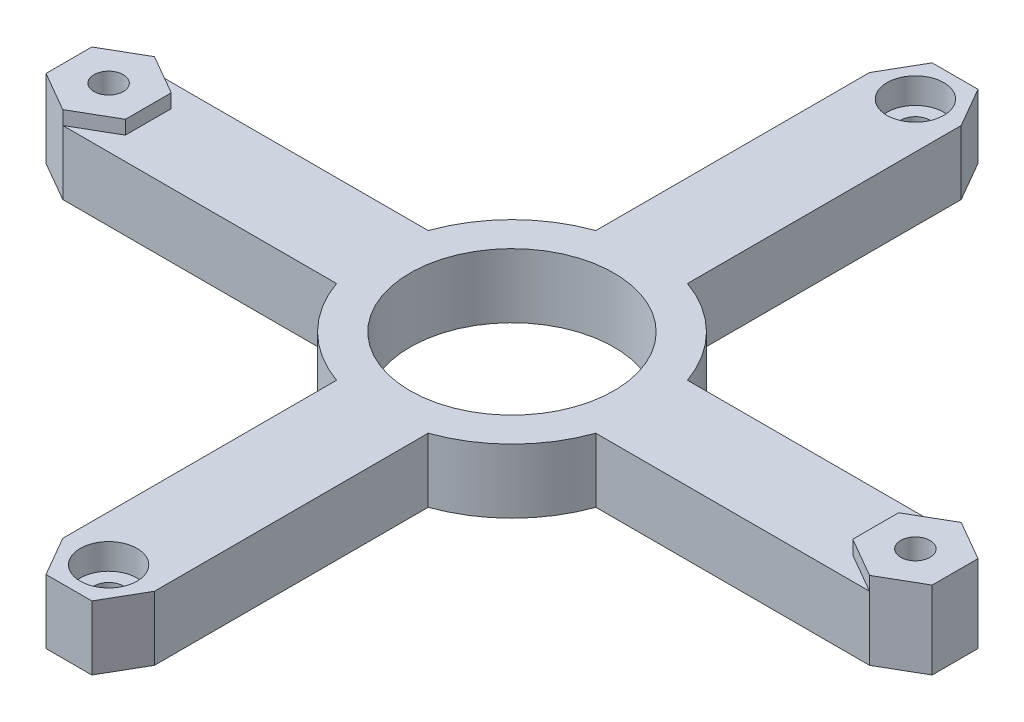
SolidWorks part; units mm, degrees
ref_plane "Front Plane" through (0, 0, 0) normal (0, 0, 1) x (1, 0, 0)
ref_plane "Top Plane" through (0, 0, 0) normal (0, 1, 0) x (1, 0, 0)
ref_plane "Right Plane" through (0, 0, 0) normal (1, 0, 0) x (0, 0, -1)
sketch "Sketch1" plane through (0, 0, 0) normal (0, 1, 0) x (1, 0, 0)
  line L0 (0, 0) -> (0, 2984.5753) construction
  line L1 (0, 0) -> (2984.5753, 0) construction
  line L7 (44, 5) -> (48.3301, 2.5)
  line L8 (48.3301, 2.5) -> (48.3301, -2.5)
  line L13 (48.3301, -2.5) -> (44, -5)
  line L14 (5, -44) -> (2.5, -48.3301)
  line L15 (14.1421, 5) -> (44, 5)
  line L16 (2.5, -48.3301) -> (-2.5, -48.3301)
  line L17 (-2.5, -48.3301) -> (-5, -44)
  line L18 (14.1421, -5) -> (44, -5)
  line L19 (-5, -14.1421) -> (-5, -44)
  line L20 (-44, -5) -> (-48.3301, -2.5)
  line L21 (-48.3301, -2.5) -> (-48.3301, 2.5)
  line L22 (-48.3301, 2.5) -> (-44, 5)
  line L23 (-5, 44) -> (-2.5, 48.3301)
  line L24 (-2.5, 48.3301) -> (2.5, 48.3301)
  line L25 (2.5, 48.3301) -> (5, 44)
  line L26 (5, -14.1421) -> (5, -44)
  line L27 (-14.1421, 5) -> (-44, 5)
  line L28 (-44, -5) -> (-14.1421, -5)
  line L29 (-5, 44) -> (-5, 14.1421)
  line L30 (5, 44) -> (5, 14.1421)
  circle A0 centre (0, 0) radius 11.125
  arc A1 (5, -14.1421) -> (14.1421, -5) centre (0, 0) ccw
  circle A2 centre (44, 0) radius 1.6
  circle A3 centre (0, 44) radius 1.6
  circle A4 centre (-44, 0) radius 1.6
  circle A5 centre (0, -44) radius 1.6
  arc A6 (14.1421, 5) -> (5, 14.1421) centre (0, 0) ccw
  arc A7 (-5, 14.1421) -> (-14.1421, 5) centre (0, 0) ccw
  arc A8 (-14.1421, -5) -> (-5, -14.1421) centre (0, 0) ccw
  point P16 (5.0879, 44)
  point P17 (-6.1433, -14.1421)
  point P26 (48.3301, 0)
  point P49 (0, 0)
  dimension "D1" = 3.2
  dimension "D2" = 30
  dimension "D3" = 22.25
  dimension "D4" = 44
  dimension "D5" = 44
  dimension "D6" = 10
  dimension "D8" = 60
  dimension "D9" = 4
extrude "Boss-Extrude1" add sketch "Sketch1" along normal blind 7
sketch "Sketch2" plane through (0, 7, 0) normal (0, 1, 0) x (1, 0, 0)
  line L1 (-44, 5) -> (-48.3301, 2.5)
  line L2 (-48.3301, 2.5) -> (-48.3301, -2.5)
  line L3 (-48.3301, -2.5) -> (-44, -5)
  line L4 (-44, -5) -> (-39.6699, -2.5)
  line L5 (-39.6699, -2.5) -> (-39.6699, 2.5)
  line L6 (-39.6699, 2.5) -> (-44, 5)
  line L7 (48.3301, 2.5) -> (44, 5)
  line L8 (44, 5) -> (39.6699, 2.5)
  line L9 (39.6699, 2.5) -> (39.6699, -2.5)
  line L10 (39.6699, -2.5) -> (44, -5)
  line L11 (44, -5) -> (48.3301, -2.5)
  line L12 (48.3301, -2.5) -> (48.3301, 2.5)
  circle A0 centre (-44, 0) radius 4.3301 construction
  circle A1 centre (44, 0) radius 4.3301 construction
  circle A2 centre (44, 0) radius 1.6
  circle A3 centre (-44, 0) radius 1.6
  circle A4 centre (-44, 0) radius 1.6 construction
  circle A5 centre (44, 0) radius 1.6 construction
  point P22 (-42.7607, 3.7228)
  point P26 (43.526, 4.373)
extrude "Boss-Extrude2" add sketch "Sketch2" along normal blind 1.5
sketch "Sketch3" plane through (0, 7, 0) normal (0, 1, 0) x (1, 0, 0)
  circle A0 centre (0, 44) radius 3.1
  circle A1 centre (0, 44) radius 1.6 construction
  circle A2 centre (0, -44) radius 3.1
  circle A3 centre (0, -44) radius 1.6 construction
  dimension "D1" = 6.2
  dimension "D2" = 6.2
extrude "Cut-Extrude1" cut sketch "Sketch3" against normal blind 2.8
